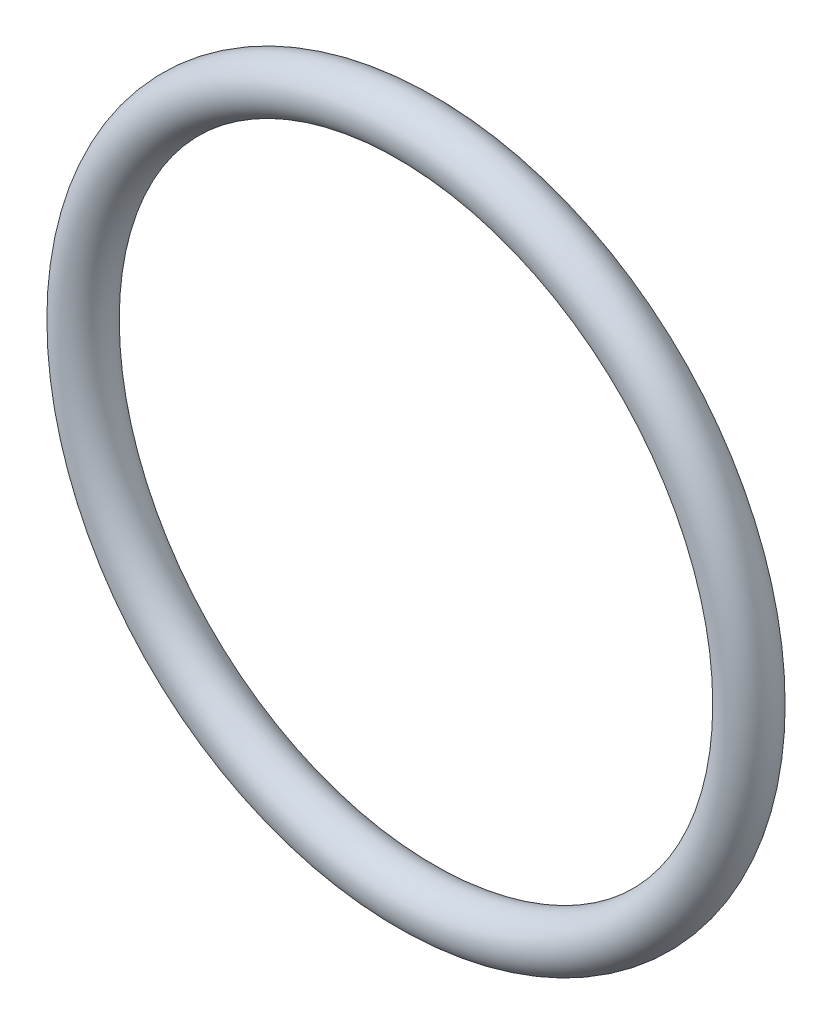
SolidWorks part; units mm, degrees
ref_plane "Front" through (0, 0, 0) normal (0, 0, 1) x (1, 0, 0)
ref_plane "Top" through (0, 0, 0) normal (0, 1, 0) x (1, 0, 0)
ref_plane "Right" through (0, 0, 0) normal (1, 0, 0) x (0, 0, -1)
sketch "Sketch1" plane through (0, 0, 0) normal (0, 0, 1) x (1, 0, 0)
  circle A0 centre (0, 0) radius 15
  dimension "d1" = 30
sketch "Sketch2" plane through (0, 0, 0) normal (0, 1, 0) x (1, 0, 0)
  circle A0 centre (-16.25, 0) radius 1.25
  point P2 (-15, 0)
  dimension "d2" = 2.5
sweep "Sweep1" add profiles "Sketch2" path "Sketch1"
ref_axis "Axis1" through (0, 0, -5.0798) along (0, 0, 1)
